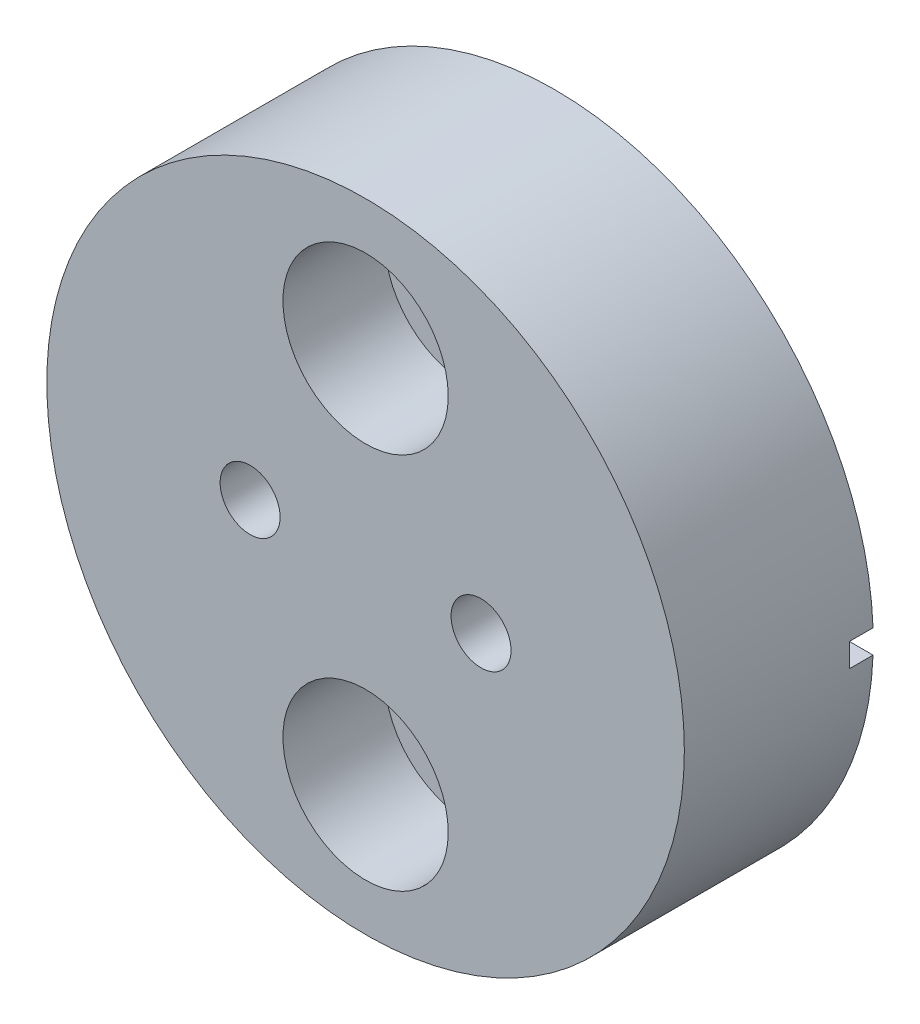
SolidWorks part; units mm, degrees
ref_plane "Front Plane" through (0, 0, 0) normal (0, 0, 1) x (1, 0, 0)
ref_plane "Top Plane" through (0, 0, 0) normal (0, 1, 0) x (1, 0, 0)
ref_plane "Right Plane" through (0, 0, 0) normal (1, 0, 0) x (0, 0, -1)
sketch "Sketch2" plane through (0, 0, 0) normal (0, 0, 1) x (1, 0, 0)
  circle A0 centre (0, 0) radius 13.5
  dimension "D1" = 27
extrude "Boss-Extrude1" add sketch "Sketch2" along normal blind 8
sketch "Sketch5" plane through (0, 0, 8) normal (0, 0, 1) x (1, 0, 0)
  circle A0 centre (0, 8) radius 2.3
  circle A1 centre (0, 0) radius 13.5 construction
  dimension "D1" = 4.6
  dimension "D2" = 8
ref_axis "Axis1" through (0, 0, -0.8) along (0, 0, 1)
extrude "Cut-Extrude4" cut sketch "Sketch5" against normal blind 10
mirror "Mirror1" about plane through (0, 0, 0) normal (0, 1, 0) of "Cut-Extrude4"
sketch "Sketch8" plane through (0, 0, 0) normal (0, 0, -1) x (-1, 0, 0)
  line L1 (-18.5, 0.5) -> (-8.5, 0.5)
  line L2 (-18.5, 0.5) -> (-18.5, -0.5)
  line L3 (-18.5, -0.5) -> (-8.5, -0.5)
  line L4 (-8.5, 0.5) -> (-8.5, -0.5)
  line L5 (-18.5, 0.5) -> (-8.5, -0.5) construction
  line L6 (-18.5, -0.5) -> (-8.5, 0.5) construction
  circle A0 centre (0, 0) radius 13.5 construction
  point P0 (-13.5, 0)
  dimension "D1" = 1
  dimension "D2" = 10
extrude "Cut-Extrude5" cut sketch "Sketch8" against normal blind 1
mirror "Mirror2" about plane through (0, 0, 0) normal (1, 0, 0) of "Cut-Extrude5"
sketch "Sketch11" plane through (0, 0, 8) normal (0, 0, 1) x (1, 0, 0)
  circle A0 centre (0, 8) radius 3.5
  dimension "D1" = 7
extrude "Cut-Extrude6" cut sketch "Sketch11" against normal blind 4.32
mirror "Mirror3" about plane through (0, 0, 0) normal (0, 1, 0) of "Cut-Extrude6"
sketch "Sketch12" plane through (0, 0, 8) normal (0, 0, 1) x (1, 0, 0)
  circle A0 centre (4.89, 0) radius 1.27
  circle A1 centre (-4.89, 0) radius 1.27
  dimension "D1" = 2.54
  dimension "D2" = 2.54
  dimension "D3" = 9.78
  dimension "D4" = 4.89
extrude "Cut-Extrude7" cut sketch "Sketch12" against normal blind 32.5
sketch "Sketch13" plane through (0, 0, 8) normal (0, 0, 1) x (1, 0, 0)
  circle A0 centre (0, 0) radius 7.94
  dimension "D1" = 15.88
